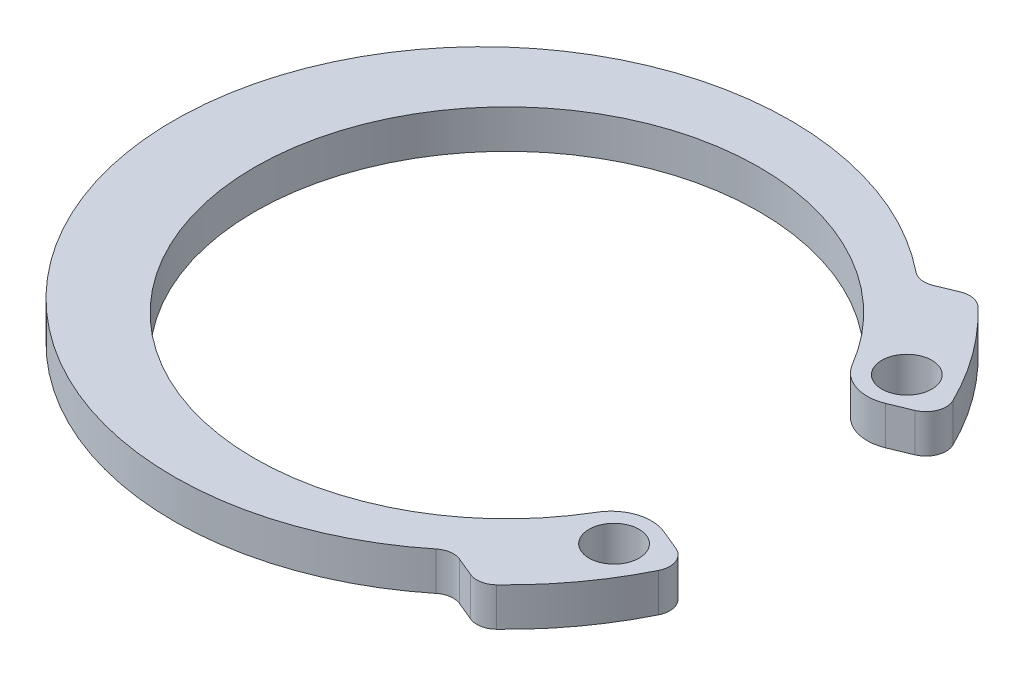
SolidWorks part; units mm, degrees
ref_plane "Front Plane" through (0, 0, 0) normal (0, 0, 1) x (1, 0, 0)
ref_plane "Top Plane" through (0, 0, 0) normal (0, 1, 0) x (1, 0, 0)
ref_plane "Right Plane" through (0, 0, 0) normal (1, 0, 0) x (0, 0, -1)
sketch "Sketch1" plane through (0, 0, 0) normal (0, 1, 0) x (1, 0, 0)
  line L0 (0, 0) -> (3.9874, 5.1965) construction
  line L1 (3.9874, 5.1965) -> (5.2658, 6.8625) construction
  line L2 (0, 0) -> (6.0514, 2.5066) construction
  line L3 (6.0514, 2.5066) -> (7.9916, 3.3102) construction
  line L4 (0, 0) -> (6.0514, -2.5066) construction
  line L5 (6.0514, -2.5066) -> (7.9916, -3.3102) construction
  line L6 (0, 0) -> (3.9874, -5.1965) construction
  line L7 (3.9874, -5.1965) -> (5.2658, -6.8625) construction
  line L8 (6.6287, -5.0864) -> (0, 0) construction
  line L9 (0, 0) -> (8.65, 0) construction
  line L10 (7.9916, 3.3102) -> (7.9916, -3.3102) construction
  line L11 (7.9916, -3.3102) -> (5.2658, -6.8625) construction
  line L12 (7.9916, 3.3102) -> (5.2658, 6.8625) construction
  line L13 (6.6287, 5.0864) -> (0, 0) construction
  line L14 (-6.55, 0) -> (-8.65, 0) construction
  circle A0 centre (0, 0) radius 8.65 construction
  circle A1 centre (0, 0) radius 6.55 construction
  arc A4 (7.0215, 2.9084) -> (6.0295, 4.6266) centre (0, 0) ccw construction
  arc A7 (7.0215, -2.9084) -> (6.0295, -4.6266) centre (0, 0) cw construction
  circle A8 centre (6.5818, -3.8) radius 0.65 construction
  circle A9 centre (6.5818, 3.8) radius 0.65 construction
  point P20 (7.9916, 0)
  dimension "Ring OD" = 17.3
  dimension "R" = 1.3
  dimension "D1" = 30
  dimension "D3" = 45
  dimension "S" = 2.1
sketch "Sketch2" plane through (0, 0, 0) normal (1, 0, 0) x (0, 0, -1)
  line L3 (8.65, 0) -> (-8.65, 0) construction
  line L7 (8.65, 0.5) -> (8.65, -0.5) construction
  dimension "Ring Thickness" = 1
sketch "Sketch3" plane through (0, 0, 0) normal (0, 1, 0) x (1, 0, 0)
  line L1 (-8.65, 0) -> (-6.55, 0) construction
  line L2 (6.0514, -2.5066) -> (7.9916, -3.3102) construction
  line L3 (3.9874, -5.1965) -> (5.2658, -6.8625) construction
  line L5 (4.9211, 6.1515) -> (5.4155, 6.3563)
  line L6 (6.9541, 2.8805) -> (7.4908, 3.1028)
  line L7 (6.9541, -2.8805) -> (7.4908, -3.1028)
  line L8 (4.9211, -6.1515) -> (5.4155, -6.3563)
  line L9 (3.9874, 5.1965) -> (5.2658, 6.8625) construction
  line L10 (6.0514, 2.5066) -> (7.9916, 3.3102) construction
  line L11 (0, 0) -> (6.0514, 2.5066) construction
  arc A1 (5.6471, 3.3186) -> (5.6471, -3.3186) centre (0, 0) ccw
  circle A2 centre (0, 0) radius 6.55 construction
  arc A3 (4.3902, 6.2282) -> (4.3902, -6.2282) centre (-0.6426, 0) ccw
  circle A4 centre (0, 0) radius 8.65 construction
  arc A6 (5.9793, 6.2506) -> (7.761, 3.8197) centre (0, 0) cw
  arc A7 (5.4155, -6.3563) -> (5.9793, -6.2506) centre (5.6164, -5.8712) ccw
  arc A8 (5.9793, -6.2506) -> (7.761, -3.8197) centre (0, 0) ccw
  circle A9 centre (6.5818, -3.8) radius 0.65
  circle A10 centre (6.5818, 3.8) radius 0.65
  circle A11 centre (6.5818, 3.8) radius 0.65 construction
  circle A12 centre (6.5818, -3.8) radius 0.65 construction
  arc A13 (4.3902, -6.2282) -> (4.9211, -6.1515) centre (4.7202, -6.6365) cw
  arc A14 (7.4908, -3.1028) -> (7.761, -3.8197) centre (7.2899, -3.5878) cw
  arc A15 (6.9541, -2.8805) -> (5.6471, -3.3186) centre (6.5523, -3.8506) ccw
  arc A16 (6.9541, 2.8805) -> (5.6471, 3.3186) centre (6.5523, 3.8506) cw
  arc A17 (7.4908, 3.1028) -> (7.761, 3.8197) centre (7.2899, 3.5878) ccw
  arc A18 (5.4155, 6.3563) -> (5.9793, 6.2506) centre (5.6164, 5.8712) cw
  arc A19 (4.3902, 6.2282) -> (4.9211, 6.1515) centre (4.7202, 6.6365) ccw
  arc A20 (7.0215, 2.9084) -> (6.0295, 4.6266) centre (0, 0) ccw construction
  arc A21 (6.0295, -4.6266) -> (7.0215, -2.9084) centre (0, 0) ccw construction
  point P24 (4.6266, 6.0295)
  point P30 (4.6266, -6.0295)
  dimension "D1" = 0.525
  dimension "D2" = 1.05
extrude "Boss-Extrude1" add sketch "Sketch3" along normal up to vertex (0.5 mm away) and the other way up to vertex (0.5 mm away) up to point (0, 0.5, -8.65) other way up to point (0, -0.5, -8.65)
sketch "Sketch4" plane through (0, 0, 0) normal (0, 1, 0) x (1, 0, 0)
  line L0 (0, -7.9816) -> (0, 7.9816) construction
  arc A0 (4.3902, 6.2282) -> (4.3902, -6.2282) centre (-0.6426, 0) ccw construction
  point P7 (0, 0)
  point P9 (0, -7.9816)
sketch "Esquisse1" plane through (0, 0.5, 0) normal (0, 1, 0) x (1, 0, 0)
  circle A0 centre (0, 0) radius 8 construction
  dimension "D1" = 16
equation "\"D1@Sketch3\"=\"S@Sketch1\"/4"
equation "\"D2@Sketch3\"=\"S@Sketch1\"/2"
